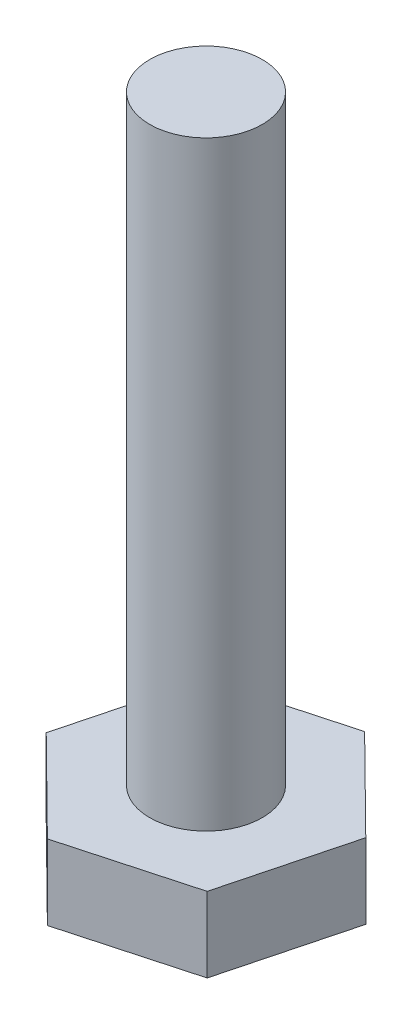
SolidWorks part; units mm, degrees
ref_plane "Front Plane" through (0, 0, 0) normal (0, 0, 1) x (1, 0, 0)
ref_plane "Top Plane" through (0, 0, 0) normal (0, 1, 0) x (1, 0, 0)
ref_plane "Right Plane" through (0, 0, 0) normal (1, 0, 0) x (0, 0, -1)
ref_axis "Axis1" through (0, -55, 0) along (0, 1, 0)
sketch "Sketch1" plane through (0, 0, 0) normal (0, 1, 0) x (1, 0, 0)
  line L1 (2.4652, -2.4337) -> (3.3402, 0.9181)
  line L2 (3.3402, 0.9181) -> (0.875, 3.3518)
  line L3 (0.875, 3.3518) -> (-2.4652, 2.4337)
  line L4 (-2.4652, 2.4337) -> (-3.3402, -0.9181)
  line L5 (-3.3402, -0.9181) -> (-0.875, -3.3518)
  line L6 (-0.875, -3.3518) -> (2.4652, -2.4337)
  circle A0 centre (0, 0) radius 3 construction
extrude "Boss-Extrude1" add sketch "Sketch1" along normal blind 2
sketch "Sketch2" plane through (0, 2, 0) normal (0, 1, 0) x (1, 0, 0)
  circle A0 centre (0, 0) radius 1.5
  dimension "D1" = 3
extrude "Boss-Extrude2" add sketch "Sketch2" along normal blind 16
equation "\"Length\"= 16"
equation "\"D1@Boss-Extrude2\"=\"Length\""
